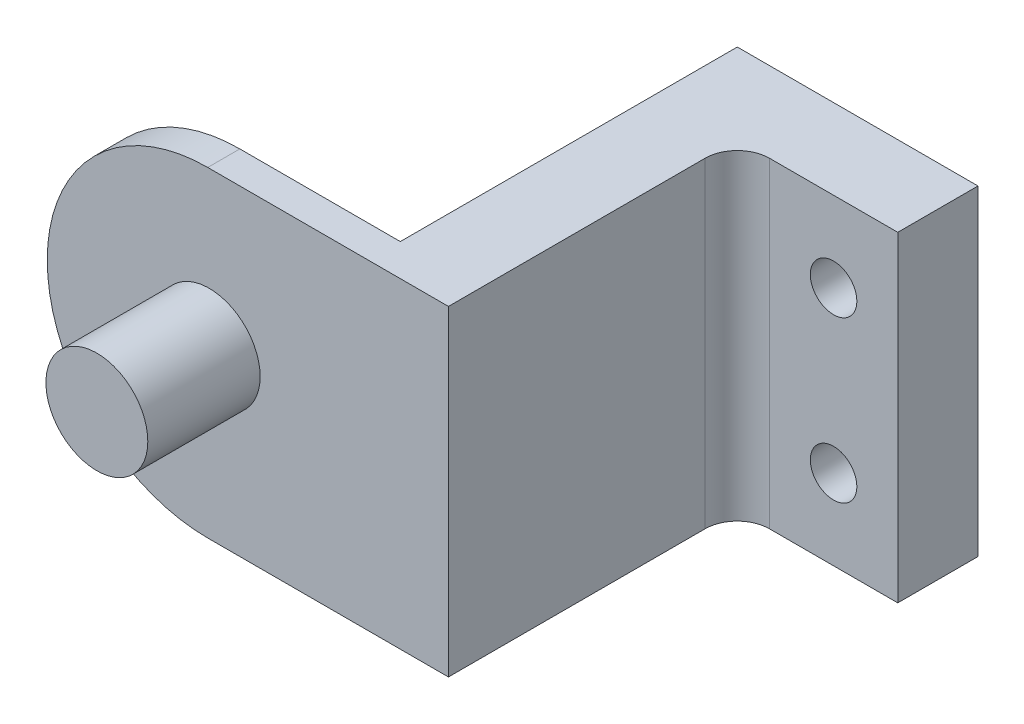
SolidWorks part; units mm, degrees
material "ABS"
ref_plane "Front" through (0, 0, 0) normal (0, 0, 1) x (1, 0, 0)
ref_plane "Top" through (0, 0, 0) normal (0, 1, 0) x (1, 0, 0)
ref_plane "Right" through (0, 0, 0) normal (1, 0, 0) x (0, 0, -1)
sketch "Esquisse1" plane through (0, 0, 0) normal (0, 0, 1) x (1, 0, 0)
  line L1 (-2.5, 10) -> (2.5, 10)
  line L2 (-2.5, 10) -> (-2.5, -10)
  line L3 (-2.5, -10) -> (2.5, -10)
  line L4 (2.5, 10) -> (2.5, -10)
  line L5 (-2.5, 10) -> (2.5, -10) construction
  line L6 (-2.5, -10) -> (2.5, 10) construction
  point P0 (0, 0)
  dimension "D1" = 5
  dimension "D2" = 20
extrude "Boss.-Extru.1" add sketch "Esquisse1" along normal blind 21
sketch "Esquisse2" plane through (0, 0, 21) normal (0, 0, 1) x (1, 0, 0)
  line L0 (-2.5, -10) -> (2.5, -10) construction
  line L1 (2.5, 10) -> (-22.5, 10)
  line L2 (2.5, 10) -> (2.5, -10)
  line L3 (2.5, -10) -> (-22.5, -10)
  line L4 (-22.5, 10) -> (-22.5, -10)
  dimension "D1" = 25
extrude "Boss.-Extru.2" add sketch "Esquisse2" along normal blind 2
sketch "Esquisse3" plane through (0, 0, 23) normal (0, 0, 1) x (1, 0, 0)
  line L0 (2.5, 10) -> (-22.5, 10) construction
  line L2 (-2.5, 10) -> (-2.5, -10) construction
  circle A0 centre (-12.41, 0.35) radius 3.175
  dimension "D1" = 6.35
  dimension "D2" = 9.65
  dimension "D3" = 9.91
extrude "Boss.-Extru.3" add sketch "Esquisse3" along normal blind 7
fillet "Congé1" radius 10 2 edges at (-22.5, 10, 22) (-22.5, -10, 22)
sketch "Esquisse5" plane through (2.5, 0, 0) normal (1, 0, 0) x (0, 0, -1)
  line L0 (-23, -10) -> (0, -10) construction
  line L1 (0, 10) -> (-5, 10)
  line L2 (0, 10) -> (0, -10)
  line L3 (0, -10) -> (-5, -10)
  line L4 (-5, 10) -> (-5, -10)
  dimension "D1" = 5
extrude "Boss.-Extru.4" add sketch "Esquisse5" along normal blind 10
fillet "Congé2" radius 2 1 edges at (2.5, 0, 5)
sketch "Esquisse6" plane through (0, 0, 5) normal (0, 0, 1) x (1, 0, 0)
  line L0 (12.5, 10) -> (4.5, 10) construction
  line L1 (12.5, 10) -> (12.5, -10) construction
  circle A0 centre (8.5, 5) radius 1.45
  circle A1 centre (8.5, -5) radius 1.45
  dimension "D1" = 2.9
  dimension "D2" = 10
  dimension "D3" = 5
  dimension "D4" = 4
extrude "Enlèv. mat.-Extru.1" cut sketch "Esquisse6" against normal up to next
